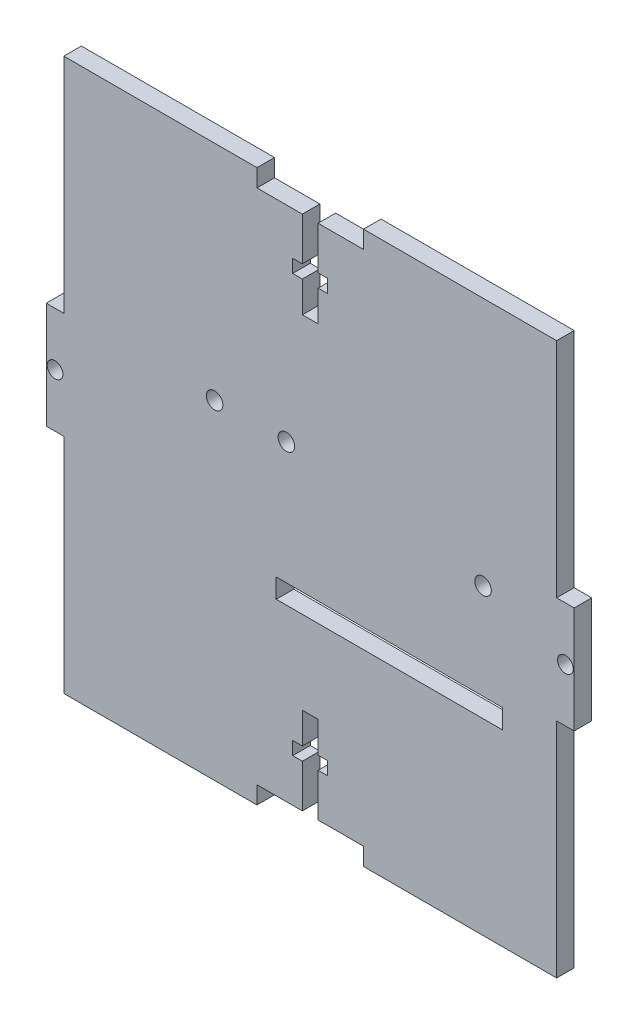
SolidWorks part; units mm, degrees
ref_plane "Front Plane" through (0, 0, 0) normal (0, 0, 1) x (1, 0, 0)
ref_plane "Top Plane" through (0, 0, 0) normal (0, 1, 0) x (1, 0, 0)
ref_plane "Right Plane" through (0, 0, 0) normal (1, 0, 0) x (0, 0, -1)
sketch "Sketch1" plane through (0, 0, 0) normal (0, 0, 1) x (1, 0, 0)
  line L0 (-44.645, 50) -> (-14.8817, 50)
  line L1 (-44.645, -50) -> (44.645, -50)
  line L2 (-44.645, -50) -> (-44.645, 50)
  line L3 (-44.645, 50) -> (44.645, 50) construction
  line L4 (44.645, -50) -> (44.645, 50)
  line L5 (-44.645, -50) -> (44.645, 50) construction
  line L6 (-44.645, 50) -> (44.645, -50) construction
  line L7 (-14.8817, 50) -> (14.8817, 50)
  line L8 (14.8817, 50) -> (44.645, 50)
  point P0 (0, 0)
  dimension "D1" = 89.29
  dimension "D2" = 100
extrude "Boss-Extrude1" add sketch "Sketch1" along normal blind 3.18
sketch "Sketch3" [suppressed] plane through (0, 0, 0) normal (0, 0, -1) x (-1, 0, 0)
  line L0 (-36.2767, 30.4733) -> (-36.2767, -65.2767)
  line L1 (-36.2767, -65.2767) -> (29.0733, -65.2767)
  line L2 (29.0733, -65.2767) -> (29.0733, 30.4733)
  line L3 (29.0733, 30.4733) -> (5.8983, 30.4733)
  line L4 (5.8983, 30.4733) -> (5.8983, 33.4733)
  line L5 (5.8983, 33.4733) -> (-13.1017, 33.4733)
  line L6 (-13.1017, 33.4733) -> (-13.1017, 30.4733)
  line L7 (-13.1017, 30.4733) -> (-36.2767, 30.4733)
  line L8 (29.0733, 40.4733) -> (-36.2767, 40.4733)
  line L9 (29.0733, -65.2767) -> (29.0733, 40.4733)
  line L10 (-36.2767, -65.2767) -> (29.0733, -65.2767)
  line L11 (-36.2767, 40.4733) -> (-36.2767, -65.2767)
  line L12 (-36.2767, -65.2767) -> (-36.2767, -73.645) construction
  line L13 (44.645, -73.645) -> (-44.645, -73.645) construction
  line L14 (-36.2767, -65.2767) -> (-44.645, -65.2767) construction
  line L15 (-44.645, -73.645) -> (-44.645, 73.645) construction
  dimension "D1" = 65.35
  dimension "D2" = 95.75
  dimension "D3" = 105.75
  dimension "D4" = 19
  dimension "D5" = 3
extrude "Cut-Extrude1" [suppressed] cut sketch "Sketch3" against normal through all contours L6 L7 L0 L1 L2 L3 L4 L5
sketch "Sketch9" [suppressed] plane through (-44.645, 0, 0) normal (-1, 0, 0) x (0, 0, 1)
  line L0 (0, 0) -> (3.18, 0) construction
  line L1 (0, 73.645) -> (0, -73.645) construction
  line L2 (3.18, 73.645) -> (3.18, -73.645) construction
  line L4 (0, -9.65) -> (3.18, -9.65)
  line L5 (0, -9.65) -> (0, 9.65)
  line L6 (0, 9.65) -> (3.18, 9.65)
  line L7 (3.18, -9.65) -> (3.18, 9.65)
  line L8 (0, -9.65) -> (3.18, 9.65) construction
  line L9 (0, 9.65) -> (3.18, -9.65) construction
  point P6 (1.59, 0)
  dimension "D1" = 19.3
extrude "Boss-Extrude4" [suppressed] add sketch "Sketch9" along normal blind 3.18
sketch "Sketch10" [suppressed] plane through (0, 0, 3.18) normal (0, 0, 1) x (1, 0, 0)
  line L0 (-46.235, 9.65) -> (-46.235, -9.65) construction
  line L1 (-47.825, 9.65) -> (-44.645, 9.65) construction
  line L2 (-47.825, -9.65) -> (-44.645, -9.65) construction
  circle A0 centre (-46.235, 0) radius 1.425
extrude "Cut-Extrude4" [suppressed] cut sketch "Sketch10" against normal through all
mirror "Mirror1" [suppressed] about plane through (0, 0, 0) normal (1, 0, 0)
sketch "Sketch18" plane through (44.645, 0, 0) normal (1, 0, 0) x (0, 0, -1)
  line L0 (0, 0) -> (-3.18, 0) construction
  line L1 (0, -50) -> (0, 50) construction
  line L2 (-3.18, -50) -> (-3.18, 50) construction
  line L4 (-3.18, -9.65) -> (0, -9.65)
  line L5 (-3.18, -9.65) -> (-3.18, 9.65)
  line L6 (-3.18, 9.65) -> (0, 9.65)
  line L7 (0, -9.65) -> (0, 9.65)
  line L8 (-3.18, -9.65) -> (0, 9.65) construction
  line L9 (-3.18, 9.65) -> (0, -9.65) construction
  point P6 (-1.59, 0)
  dimension "D1" = 19.3
extrude "Boss-Extrude8" add sketch "Sketch18" along normal blind 3.18
sketch "Sketch19" plane through (0, 0, 3.18) normal (0, 0, 1) x (1, 0, 0)
  line L0 (46.235, -9.65) -> (46.235, 9.65) construction
  line L1 (47.825, -9.65) -> (44.645, -9.65) construction
  line L2 (47.825, 9.65) -> (44.645, 9.65) construction
  circle A0 centre (46.235, 0) radius 1.425
extrude "Cut-Extrude8" cut sketch "Sketch19" against normal through all
mirror "Mirror2" about plane through (0, 0, 0) normal (1, 0, 0) of "Boss-Extrude8", "Cut-Extrude8"
sketch "Sketch20" [suppressed] plane through (0, 0, 3.18) normal (0, 0, 1) x (1, 0, 0)
  line L0 (0, 70.465) -> (0, 0) construction
  line L1 (44.645, 73.645) -> (-44.645, 73.645) construction
  line L2 (-9.65, 73.645) -> (9.65, 73.645)
  line L3 (9.65, 73.645) -> (9.65, 70.465)
  line L4 (9.65, 70.465) -> (1.425, 70.465)
  line L5 (1.425, 70.465) -> (1.425, 62.665)
  line L6 (1.425, 62.665) -> (3.175, 62.665)
  line L7 (3.175, 62.665) -> (3.175, 60.285)
  line L8 (3.175, 60.285) -> (1.425, 60.285)
  line L9 (1.425, 60.285) -> (1.425, 54.665)
  line L10 (1.425, 54.665) -> (-1.425, 54.665)
  line L11 (-1.425, 54.665) -> (-1.425, 60.285)
  line L12 (-1.425, 60.285) -> (-3.175, 60.285)
  line L13 (-3.175, 60.285) -> (-3.175, 62.665)
  line L14 (-3.175, 62.665) -> (-1.425, 62.665)
  line L15 (-1.425, 62.665) -> (-1.425, 70.465)
  line L16 (-1.425, 70.465) -> (-9.65, 70.465)
  line L17 (-9.65, 70.465) -> (-9.65, 73.645)
  dimension "D1" = 19.3
  dimension "D2" = 3.18
  dimension "D3" = 15.8
  dimension "D4" = 6.35
  dimension "D5" = 2.38
  dimension "D6" = 2.85
  dimension "D7" = 7.8
extrude "Cut-Extrude9" [suppressed] cut sketch "Sketch20" against normal through all
mirror "Mirror3" [suppressed] about plane through (0, 0, 0) normal (0, 1, 0)
sketch "Sketch23" [suppressed] plane through (0, 0, 3.18) normal (0, 0, 1) x (1, 0, 0)
  line L0 (-44.645, 13.995) -> (-44.645, 33.295)
  line L1 (-44.645, 73.645) -> (-44.645, -73.645) construction
  line L2 (-44.645, 33.295) -> (-41.465, 33.295)
  line L3 (-41.465, 33.295) -> (-41.465, 25.07)
  line L4 (-41.465, 25.07) -> (-33.665, 25.07)
  line L5 (-33.665, 25.07) -> (-33.665, 26.82)
  line L6 (-33.665, 26.82) -> (-31.285, 26.82)
  line L7 (-31.285, 26.82) -> (-31.285, 25.07)
  line L8 (-31.285, 25.07) -> (-25.665, 25.07)
  line L9 (-25.665, 25.07) -> (-25.665, 22.22)
  line L10 (-25.665, 22.22) -> (-31.285, 22.22)
  line L11 (-31.285, 22.22) -> (-31.285, 20.47)
  line L12 (-31.285, 20.47) -> (-33.665, 20.47)
  line L13 (-33.665, 20.47) -> (-33.665, 22.22)
  line L14 (-33.665, 22.22) -> (-41.465, 22.22)
  line L15 (-41.465, 22.22) -> (-41.465, 13.995)
  line L16 (-41.465, 13.995) -> (-44.645, 13.995)
  line L17 (44.645, 73.645) -> (-44.645, 73.645) construction
  line L19 (-25.665, 23.645) -> (-44.645, 23.645) construction
  line L20 (-44.645, -33.295) -> (-44.645, -13.995)
  line L21 (-44.645, -13.995) -> (-41.465, -13.995)
  line L22 (-41.465, -13.995) -> (-41.465, -22.22)
  line L23 (-41.465, -22.22) -> (-33.665, -22.22)
  line L24 (-33.665, -22.22) -> (-33.665, -20.47)
  line L25 (-33.665, -20.47) -> (-31.285, -20.47)
  line L26 (-31.285, -20.47) -> (-31.285, -22.22)
  line L27 (-31.285, -22.22) -> (-25.665, -22.22)
  line L28 (-25.665, -22.22) -> (-25.665, -25.07)
  line L29 (-25.665, -25.07) -> (-31.285, -25.07)
  line L30 (-31.285, -25.07) -> (-31.285, -26.82)
  line L31 (-31.285, -26.82) -> (-33.665, -26.82)
  line L32 (-33.665, -26.82) -> (-33.665, -25.07)
  line L33 (-33.665, -25.07) -> (-41.465, -25.07)
  line L34 (-41.465, -25.07) -> (-41.465, -33.295)
  line L35 (-41.465, -33.295) -> (-44.645, -33.295)
  line L36 (-44.645, -23.645) -> (-25.665, -23.645) construction
  line L37 (-44.645, -73.645) -> (44.645, -73.645) construction
  dimension "D1" = 50
  dimension "D2" = 19.3
  dimension "D3" = 3.18
  dimension "D4" = 15.8
  dimension "D5" = 6.35
  dimension "D6" = 2.85
  dimension "D7" = 7.8
  dimension "D8" = 2.38
  dimension "D9" = 19.3
  dimension "D10" = 3.18
  dimension "D11" = 7.8
  dimension "D12" = 15.8
  dimension "D13" = 6.35
  dimension "D14" = 2.85
  dimension "D15" = 2.38
  dimension "D16" = 50
  dimension "D17" = 1.75
extrude "Cut-Extrude10" [suppressed] cut sketch "Sketch23" against normal through all
sketch "Sketch24" [suppressed] plane through (0, 0, 3.18) normal (0, 0, 1) x (1, 0, 0)
  line L0 (44.645, -13.995) -> (44.645, -33.295)
  line L1 (44.645, -73.645) -> (44.645, 73.645) construction
  line L2 (44.645, -33.295) -> (41.465, -33.295)
  line L3 (41.465, -33.295) -> (41.465, -25.07)
  line L4 (41.465, -25.07) -> (33.665, -25.07)
  line L5 (33.665, -25.07) -> (33.665, -26.82)
  line L6 (33.665, -26.82) -> (31.285, -26.82)
  line L7 (31.285, -26.82) -> (31.285, -25.07)
  line L8 (31.285, -25.07) -> (25.665, -25.07)
  line L9 (25.665, -25.07) -> (25.665, -22.22)
  line L10 (25.665, -22.22) -> (31.285, -22.22)
  line L11 (31.285, -22.22) -> (31.285, -20.47)
  line L12 (31.285, -20.47) -> (33.665, -20.47)
  line L13 (33.665, -20.47) -> (33.665, -22.22)
  line L14 (33.665, -22.22) -> (41.465, -22.22)
  line L15 (41.465, -22.22) -> (41.465, -13.995)
  line L16 (41.465, -13.995) -> (44.645, -13.995)
  line L17 (25.665, -23.645) -> (44.645, -23.645) construction
  line L18 (-44.645, -73.645) -> (44.645, -73.645) construction
  line L19 (44.645, 33.295) -> (44.645, 13.995)
  line L20 (44.645, 13.995) -> (41.465, 13.995)
  line L21 (41.465, 13.995) -> (41.465, 22.22)
  line L22 (41.465, 22.22) -> (33.665, 22.22)
  line L23 (33.665, 22.22) -> (33.665, 20.47)
  line L24 (33.665, 20.47) -> (31.285, 20.47)
  line L25 (31.285, 20.47) -> (31.285, 22.22)
  line L26 (31.285, 22.22) -> (25.665, 22.22)
  line L27 (25.665, 22.22) -> (25.665, 25.07)
  line L28 (25.665, 25.07) -> (31.285, 25.07)
  line L29 (31.285, 25.07) -> (31.285, 26.82)
  line L30 (31.285, 26.82) -> (33.665, 26.82)
  line L31 (33.665, 26.82) -> (33.665, 25.07)
  line L32 (33.665, 25.07) -> (41.465, 25.07)
  line L33 (41.465, 25.07) -> (41.465, 33.295)
  line L34 (41.465, 33.295) -> (44.645, 33.295)
  line L35 (25.665, 23.645) -> (44.645, 23.645) construction
  line L36 (44.645, 73.645) -> (-44.645, 73.645) construction
  dimension "D1" = 19.3
  dimension "D2" = 3.18
  dimension "D3" = 15.8
  dimension "D4" = 7.8
  dimension "D5" = 6.35
  dimension "D6" = 2.85
  dimension "D7" = 2.38
  dimension "D8" = 50
  dimension "D9" = 19.3
  dimension "D10" = 3.18
  dimension "D11" = 7.8
  dimension "D12" = 15.8
  dimension "D13" = 6.35
  dimension "D14" = 2.85
  dimension "D15" = 2.38
  dimension "D16" = 50
extrude "Cut-Extrude11" [suppressed] cut sketch "Sketch24" against normal through all
sketch "Sketch25" [suppressed] plane through (0, 0, 3.18) normal (0, 0, 1) x (1, 0, 0)
  line L0 (9.65, -73.645) -> (-9.65, -73.645)
  line L1 (-44.645, -73.645) -> (44.645, -73.645) construction
  line L2 (-9.65, -73.645) -> (-9.65, -70.465)
  line L3 (-9.65, -70.465) -> (-1.425, -70.465)
  line L4 (-1.425, -70.465) -> (-1.425, -62.665)
  line L5 (-1.425, -62.665) -> (-3.175, -62.665)
  line L6 (-3.175, -62.665) -> (-3.175, -60.285)
  line L7 (-3.175, -60.285) -> (-1.425, -60.285)
  line L8 (-1.425, -60.285) -> (-1.425, -54.665)
  line L9 (-1.425, -54.665) -> (1.425, -54.665)
  line L10 (1.425, -54.665) -> (1.425, -60.285)
  line L11 (1.425, -60.285) -> (3.175, -60.285)
  line L12 (3.175, -60.285) -> (3.175, -62.665)
  line L13 (3.175, -62.665) -> (1.425, -62.665)
  line L14 (1.425, -62.665) -> (1.425, -70.465)
  line L15 (1.425, -70.465) -> (9.65, -70.465)
  line L16 (9.65, -70.465) -> (9.65, -73.645)
  line L17 (0, -73.645) -> (0, 0) construction
  dimension "D1" = 19.3
  dimension "D2" = 3.18
  dimension "D3" = 15.8
  dimension "D4" = 7.8
  dimension "D5" = 6.35
  dimension "D6" = 2.85
  dimension "D7" = 2.38
extrude "Cut-Extrude12" [suppressed] cut sketch "Sketch25" against normal through all
sketch "Sketch26" plane through (0, 0, 3.18) normal (0, 0, 1) x (1, 0, 0)
  line L0 (-9.65, 50) -> (9.65, 50)
  line L1 (44.645, 50) -> (-44.645, 50) construction
  line L2 (9.65, 50) -> (9.65, 46.82)
  line L3 (9.65, 46.82) -> (1.425, 46.82)
  line L4 (1.425, 46.82) -> (1.425, 39.02)
  line L5 (1.425, 39.02) -> (3.175, 39.02)
  line L6 (3.175, 39.02) -> (3.175, 36.64)
  line L7 (3.175, 36.64) -> (1.425, 36.64)
  line L8 (1.425, 36.64) -> (1.425, 31.02)
  line L9 (1.425, 31.02) -> (-1.425, 31.02)
  line L10 (-1.425, 31.02) -> (-1.425, 36.64)
  line L11 (-1.425, 36.64) -> (-3.175, 36.64)
  line L12 (-3.175, 36.64) -> (-3.175, 39.02)
  line L13 (-3.175, 39.02) -> (-1.425, 39.02)
  line L14 (-1.425, 39.02) -> (-1.425, 46.82)
  line L15 (-1.425, 46.82) -> (-9.65, 46.82)
  line L16 (-9.65, 46.82) -> (-9.65, 50)
  line L17 (0, 50) -> (0, -4.4192) construction
  dimension "D1" = 19.3
  dimension "D2" = 3.18
  dimension "D3" = 7.8
  dimension "D4" = 15.8
  dimension "D5" = 6.35
  dimension "D6" = 2.85
  dimension "D7" = 2.38
extrude "Cut-Extrude13" cut sketch "Sketch26" against normal through all
mirror "Mirror4" [suppressed] about plane through (0, 0, 0) normal (1, 0, 0)
mirror "Mirror5" [suppressed] about plane through (0, 0, 0) normal (1, 0, 0)
mirror "Mirror6" [suppressed] about plane through (0, 0, 0) normal (0, 1, 0)
mirror "Mirror7" about plane through (0, 0, 0) normal (0, 1, 0) of "Cut-Extrude13"
sketch "Sketch27" [suppressed] plane through (-44.645, 0, 0) normal (-1, 0, 0) x (0, 0, 1)
  line L0 (0, -36.475) -> (0, -17.175)
  line L1 (0, 73.645) -> (0, -73.645) construction
  line L2 (0, -17.175) -> (3.18, -17.175)
  line L3 (3.18, 73.645) -> (3.18, -73.645) construction
  line L4 (3.18, -17.175) -> (3.18, -36.475)
  line L5 (3.18, -36.475) -> (0, -36.475)
  line L6 (3.18, -26.825) -> (0, -26.825) construction
  line L7 (3.18, -73.645) -> (0, -73.645) construction
  dimension "D1" = 19.3
  dimension "D2" = 46.82
extrude "Boss-Extrude9" [suppressed] add sketch "Sketch27" along normal blind 3.18
sketch "Sketch28" [suppressed] plane through (0, -73.645, 0) normal (0, -1, 0) x (1, 0, 0)
  line L0 (9.65, 0) -> (-9.65, 0)
  line L1 (-44.645, 0) -> (44.645, 0) construction
  line L2 (-9.65, 0) -> (-9.65, 3.18)
  line L3 (-44.645, 3.18) -> (44.645, 3.18) construction
  line L4 (-9.65, 3.18) -> (9.65, 3.18)
  line L5 (9.65, 3.18) -> (9.65, 0)
  line L6 (0, 0) -> (0, 3.18) construction
  dimension "D1" = 19.3
extrude "Boss-Extrude10" [suppressed] add sketch "Sketch28" along normal blind 3.18
sketch "Sketch29" [suppressed] plane through (0, 0, 3.18) normal (0, 0, 1) x (1, 0, 0)
  line L0 (-47.825, -26.825) -> (-37.3062, -26.825) construction
  line L1 (-47.825, -36.475) -> (-47.825, -17.175) construction
  line L2 (-46.235, -17.175) -> (-46.235, -36.475) construction
  line L3 (-47.825, -17.175) -> (-44.645, -17.175) construction
  line L4 (-47.825, -36.475) -> (-44.645, -36.475) construction
  circle A0 centre (-46.235, -26.825) radius 1.425
extrude "Cut-Extrude14" [suppressed] cut sketch "Sketch29" against normal through all
sketch "Sketch30" [suppressed] plane through (0, 0, 3.18) normal (0, 0, 1) x (1, 0, 0)
  line L0 (0, -76.825) -> (0, -66.2855) construction
  line L1 (9.65, -76.825) -> (-9.65, -76.825) construction
  line L2 (9.65, -75.235) -> (-9.65, -75.235) construction
  line L3 (9.65, -76.825) -> (9.65, -73.645) construction
  line L4 (-9.65, -76.825) -> (-9.65, -73.645) construction
  circle A0 centre (0, -75.235) radius 1.425
extrude "Cut-Extrude15" [suppressed] cut sketch "Sketch30" against normal through all
mirror "Mirror8" [suppressed] about plane through (0, 0, 0) normal (1, 0, 0)
mirror "Mirror9" [suppressed] about plane through (0, 0, 0) normal (0, 1, 0)
sketch "Sketch31" plane through (0, 0, 3.18) normal (0, 0, 1) x (1, 0, 0)
  line L0 (14.341, -8.1358) -> (14.341, -12.6358) construction
  line L8 (5.175, -1.9558) -> (5.175, 19.3642) construction
  line L10 (-24.825, 19.3642) -> (-24.825, -1.9558) construction
  line L11 (5.175, 19.3642) -> (-24.825, 19.3642) construction
  line L16 (23.507, -9.6358) -> (39.341, -9.6358) construction
  line L17 (23.507, 19.3642) -> (23.507, -9.6358) construction
  line L18 (39.341, 19.3642) -> (23.507, 19.3642) construction
  line L19 (39.341, -9.6358) -> (39.341, 19.3642) construction
  line L26 (14.341, -15.8158) -> (14.341, -12.6358) construction
  line L29 (-24.825, -1.9558) -> (5.175, -1.9558) construction
  line L34 (20.5772, -7.1358) -> (20.5772, 11.3642) construction
  line L35 (20.5772, 11.3642) -> (8.1048, 11.3642) construction
  line L36 (8.1048, 11.3642) -> (8.1048, -7.1358) construction
  line L37 (9.7431, -8.1358) -> (18.9389, -8.1358) construction
  line L38 (14.341, -15.8158) -> (14.341, -50) construction
  line L39 (-17.325, 9.65) -> (-24.825, 9.65) construction
  line L40 (-6.159, -12.4758) -> (34.841, -12.4758)
  line L41 (-6.159, -12.4758) -> (-6.159, -15.9758)
  line L42 (-6.159, -15.9758) -> (34.841, -15.9758)
  line L43 (34.841, -12.4758) -> (34.841, -15.9758)
  line L88 (-44.645, -50) -> (-9.65, -50) construction
  line L89 (-9.65, -50) -> (-9.65, -46.82) construction
  line L90 (-9.65, -46.82) -> (-1.425, -46.82) construction
  line L91 (-1.425, -46.82) -> (-1.425, -39.02) construction
  line L92 (-1.425, -39.02) -> (-3.175, -39.02) construction
  line L93 (-3.175, -39.02) -> (-3.175, -36.64) construction
  line L94 (-3.175, -36.64) -> (-1.425, -36.64) construction
  line L95 (-1.425, -36.64) -> (-1.425, -31.02) construction
  line L96 (-1.425, -31.02) -> (1.425, -31.02) construction
  line L97 (1.425, -31.02) -> (1.425, -36.64) construction
  line L98 (1.425, -36.64) -> (3.175, -36.64) construction
  line L99 (3.175, -36.64) -> (3.175, -39.02) construction
  line L100 (3.175, -39.02) -> (1.425, -39.02) construction
  line L101 (1.425, -39.02) -> (1.425, -46.82) construction
  line L102 (1.425, -46.82) -> (9.65, -46.82) construction
  line L103 (9.65, -46.82) -> (9.65, -50) construction
  line L104 (9.65, -50) -> (44.645, -50) construction
  line L105 (44.645, -50) -> (44.645, -9.65) construction
  line L106 (44.645, -9.65) -> (47.825, -9.65) construction
  line L107 (47.825, -9.65) -> (47.825, 9.65) construction
  line L108 (47.825, 9.65) -> (44.645, 9.65) construction
  line L109 (44.645, 9.65) -> (44.645, 50) construction
  line L110 (44.645, 50) -> (9.65, 50) construction
  line L111 (9.65, 50) -> (9.65, 46.82) construction
  line L112 (9.65, 46.82) -> (1.425, 46.82) construction
  line L113 (1.425, 46.82) -> (1.425, 39.02) construction
  line L114 (1.425, 39.02) -> (3.175, 39.02) construction
  line L115 (3.175, 39.02) -> (3.175, 36.64) construction
  line L116 (3.175, 36.64) -> (1.425, 36.64) construction
  line L117 (1.425, 36.64) -> (1.425, 31.02) construction
  line L118 (1.425, 31.02) -> (-1.425, 31.02) construction
  line L119 (-1.425, 31.02) -> (-1.425, 36.64) construction
  line L120 (-1.425, 36.64) -> (-3.175, 36.64) construction
  line L121 (-3.175, 36.64) -> (-3.175, 39.02) construction
  line L122 (-3.175, 39.02) -> (-1.425, 39.02) construction
  line L123 (-1.425, 39.02) -> (-1.425, 46.82) construction
  line L124 (-1.425, 46.82) -> (-9.65, 46.82) construction
  line L125 (-9.65, 46.82) -> (-9.65, 50) construction
  line L126 (-9.65, 50) -> (-44.645, 50) construction
  line L127 (-44.645, 50) -> (-44.645, 9.65) construction
  line L128 (-44.645, 9.65) -> (-47.825, 9.65) construction
  line L129 (-47.825, 9.65) -> (-47.825, -9.65) construction
  line L130 (-47.825, -9.65) -> (-44.645, -9.65) construction
  line L131 (-44.645, -9.65) -> (-44.645, -50) construction
  line L132 (-6.159, -12.4758) -> (34.841, -15.9758) construction
  line L133 (-6.159, -15.9758) -> (34.841, -12.4758) construction
  line L134 (-17.325, 9.65) -> (-17.325, -1.9558) construction
  line L135 (31.3061, 4.8642) -> (39.341, 4.8642) construction
  line L136 (31.3061, 4.8642) -> (31.3061, 19.3642) construction
  line L137 (-17.325, 9.65) -> (-4.325, 9.65) construction
  circle A0 centre (-17.325, 9.65) radius 1.5
  circle A1 centre (31.3061, 4.8642) radius 1.5
  circle A2 centre (-4.325, 9.65) radius 1.5
  spline S4 degree 3 poles (8.1048, -7.1358) (8.1048, -7.3148) (8.1799, -7.485) (8.4092, -7.7556) (8.5582, -7.8571) (8.8762, -8.0081) (9.0479, -8.0586) (9.3919, -8.1221) (9.5665, -8.1358) (9.7431, -8.1358) knots 0 0 0 0 0.25 0.25 0.5 0.5 0.75 0.75 1 1 1 1 construction
  spline S5 degree 3 poles (18.9389, -8.1358) (19.1156, -8.1358) (19.2906, -8.1221) (19.6363, -8.0581) (19.8071, -8.0076) (20.1239, -7.857) (20.2729, -7.7556) (20.5025, -7.4843) (20.5772, -7.3148) (20.5772, -7.1358) knots 0 0 0 0 0.25 0.25 0.5 0.5 0.75 0.75 1 1 1 1 construction
  point P14 (14.341, -14.2258)
  point P46 (-44.645, 50)
  dimension "D6" = 3
  dimension "D4" = 41
  dimension "D5" = 3.5
  dimension "D7" = 7.5
  dimension "D9" = 13
extrude "Cut-Extrude16" cut sketch "Sketch31" against normal through all contours L41 L40 L43 L42 | A1 | A2 | A0
